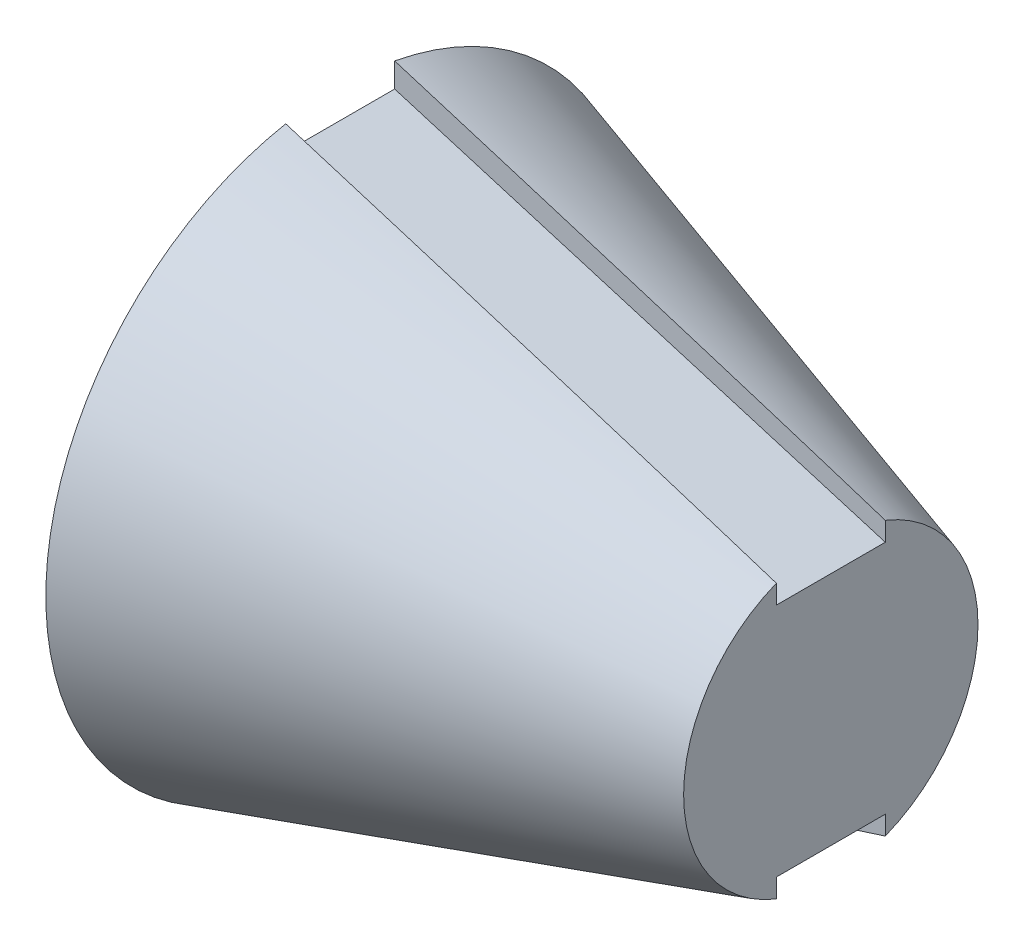
SolidWorks part; units mm, degrees
ref_plane "Front Plane" through (0, 0, 0) normal (0, 0, 1) x (1, 0, 0)
ref_plane "Top Plane" through (0, 0, 0) normal (0, 1, 0) x (1, 0, 0)
ref_plane "Right Plane" through (0, 0, 0) normal (1, 0, 0) x (0, 0, -1)
sketch "Sketch1" plane through (0, 0, 0) normal (0, 0, 1) x (1, 0, 0)
  line L0 (0, 0) -> (-50, 0)
  line L1 (-50, 0) -> (-50, 30)
  line L2 (0, 0) -> (0, 15)
  line L3 (-50, 30) -> (0, 15)
  dimension "D1" = 50
  dimension "D2" = 30
  dimension "D3" = 15
revolve "Revolve1" add sketch "Sketch1" angle 360 about L0
sketch "Sketch2" plane through (-50, 0, 0) normal (-1, 0, 0) x (0, 0, 1)
  circle A0 centre (0, 0) radius 15
  dimension "D1" = 30
extrude "Cut-Extrude1" cut sketch "Sketch2" against normal blind 10
sketch "Sketch4" plane through (0, 0, 0) normal (0, 0, 1) x (1, 0, 0)
  line L0 (0, 15) -> (0, 12)
  line L1 (-50, 30) -> (-50, -30) construction
  line L2 (0, -15) -> (0, 15) construction
  line L3 (-50, 27) -> (0, 12)
  line L4 (0, 15) -> (-50, 30) construction
  line L5 (0, 15) -> (-50, 30)
  line L6 (-50, 30) -> (-50, 27)
  line L7 (0, 0) -> (-50, 0) construction
  line L8 (0, -15) -> (0, -12)
  line L9 (-50, -30) -> (-50, -27)
  line L10 (0, -15) -> (-50, -30)
  line L11 (-50, -27) -> (0, -12)
extrude "Cut-Extrude2" cut sketch "Sketch4" against normal blind 5.55 and the other way blind 5.55
ref_plane "Plane2" through (3.3028, 11.0092, 0) normal (0.2873, 0.9578, 0) x (0.9578, -0.2873, 0)
sketch "Sketch5" plane through (3.3028, 11.0092, 0) normal (0.2873, 0.9578, 0) x (0.9578, -0.2873, 0)
  line L0 (-55.6497, 0) -> (-3.4482, 0)
  line L3 (-55.6497, -5.55) -> (-55.6497, 5.55) construction
  line L4 (-3.4482, -5.55) -> (-3.4482, 5.55) construction
